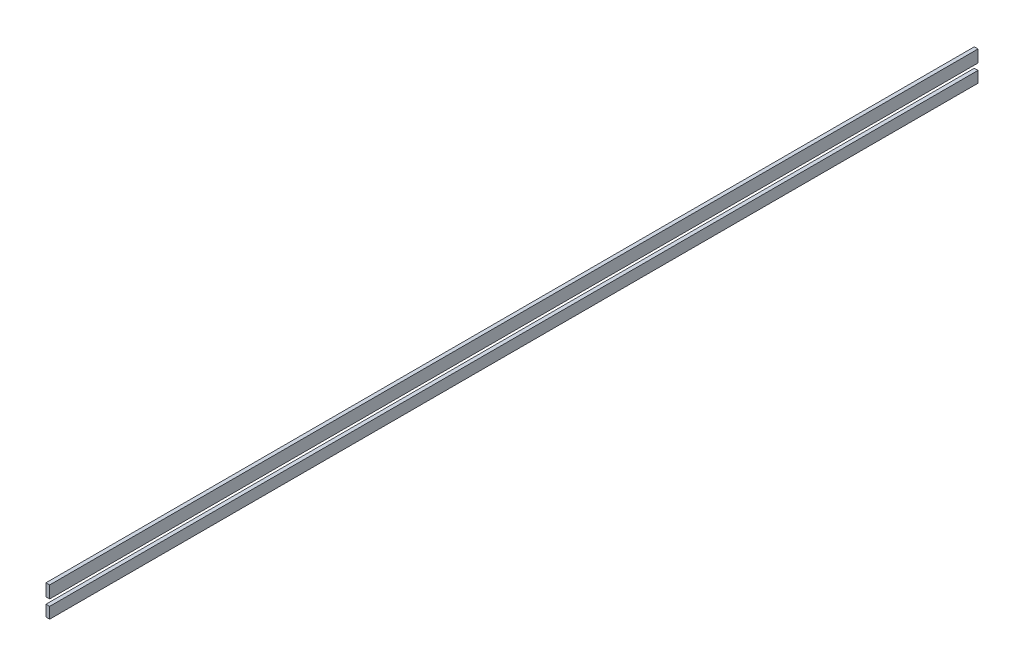
SolidWorks part; units mm, degrees
ref_plane "Front Plane" through (0, 0, 0) normal (0, 0, 1) x (1, 0, 0)
ref_plane "Top Plane" through (0, 0, 0) normal (0, 1, 0) x (1, 0, 0)
ref_plane "Right Plane" through (0, 0, 0) normal (1, 0, 0) x (0, 0, -1)
sketch "Sketch1" plane through (0, 0, 0) normal (0, 0, 1) x (1, 0, 0)
  line L1 (-1, 8) -> (1, 8)
  line L2 (-1, 8) -> (-1, 1.4286)
  line L3 (-1, 1.4286) -> (1, 1.4286)
  line L4 (1, 8) -> (1, 1.4286)
  line L5 (-1, 8) -> (1, 1.4286) construction
  line L6 (-1, 1.4286) -> (1, 8) construction
  line L7 (-1, -2) -> (1, -2)
  line L8 (-1, -2) -> (-1, -8)
  line L9 (-1, -8) -> (1, -8)
  line L10 (1, -2) -> (1, -8)
  line L11 (-1, -2) -> (1, -8) construction
  line L12 (-1, -8) -> (1, -2) construction
  point P0 (0, 4.7143)
  point P5 (0, -5)
  point P10 (0.9689, -7.59)
  dimension "D1" = 2
  dimension "D2" = 6.5714
  dimension "D3" = 2
  dimension "D4" = 6
  dimension "D5" = 16
  dimension "D6" = 1
  dimension "D7" = 1
  dimension "D8" = 8
extrude "Boss-Extrude1" add sketch "Sketch1" along normal blind 250 and the other way blind 250
